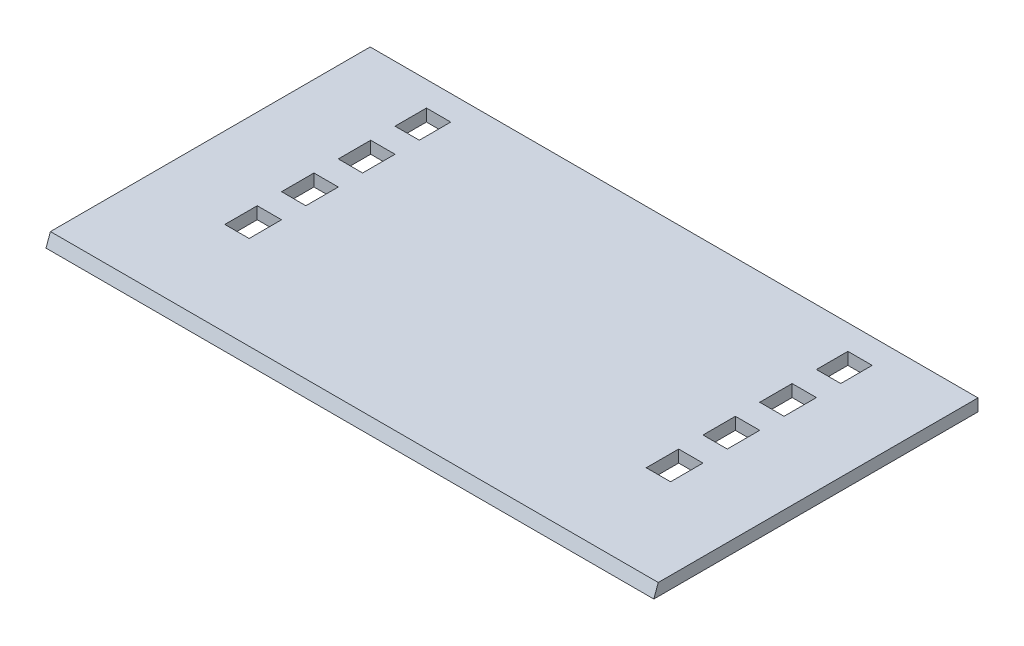
SolidWorks part; units mm, degrees
ref_plane "Plan de face" through (0, 0, 0) normal (0, 0, 1) x (1, 0, 0)
ref_plane "Plan de dessus" through (0, 0, 0) normal (0, 1, 0) x (1, 0, 0)
ref_plane "Plan de droite" through (0, 0, 0) normal (1, 0, 0) x (0, 0, -1)
sketch "Esquisse1" plane through (0, 0, 0) normal (0, 1, 0) x (1, 0, 0)
  line L1 (0, 0) -> (150, 0)
  line L2 (0, 0) -> (0, 80)
  line L3 (0, 80) -> (150, 80)
  line L4 (150, 0) -> (150, 80)
  dimension "D1" = 150
  dimension "D2" = 80
extrude "Boss.-Extru.1" add sketch "Esquisse1" along normal blind 3
chamfer "Chanfrein2" distance 3 angle 20 1 edges at (75, 3, 0) first distance on face at (75, 1.5, 0)
sketch "Esquisse2" plane through (0, 3, 0) normal (0, 1, 0) x (1, 0, 0)
  line L0 (20, 66.1284) -> (26, 66.1284) construction
  line L1 (124, 73.8859) -> (130, 73.8859)
  line L2 (124, 73.8859) -> (124, 66.1284)
  line L3 (124, 66.1284) -> (130, 66.1284)
  line L4 (130, 73.8859) -> (130, 66.1284)
  line L5 (130, 60.1284) -> (124, 60.1284)
  line L6 (130, 60.1284) -> (130, 52.1284)
  line L7 (130, 52.1284) -> (124, 52.1284)
  line L8 (124, 60.1284) -> (124, 52.1284)
  line L9 (130, 46.1284) -> (124, 46.1284)
  line L10 (130, 46.1284) -> (130, 38.1284)
  line L11 (130, 38.1284) -> (124, 38.1284)
  line L12 (124, 46.1284) -> (124, 38.1284)
  line L13 (124, 32.1284) -> (130, 32.1284)
  line L14 (124, 32.1284) -> (124, 24.1284)
  line L15 (124, 24.1284) -> (130, 24.1284)
  line L16 (130, 32.1284) -> (130, 24.1284)
  line L17 (20, 24.1284) -> (26, 24.1284)
  line L18 (20, 24.1284) -> (20, 32.1284)
  line L19 (20, 32.1284) -> (26, 32.1284)
  line L20 (26, 24.1284) -> (26, 32.1284)
  line L21 (26, 38.1284) -> (20, 38.1284)
  line L22 (26, 38.1284) -> (26, 46.1284)
  line L23 (26, 46.1284) -> (20, 46.1284)
  line L24 (20, 38.1284) -> (20, 46.1284)
  line L25 (20, 52.1284) -> (26, 52.1284)
  line L26 (20, 52.1284) -> (20, 60.1284)
  line L27 (20, 60.1284) -> (26, 60.1284)
  line L28 (26, 52.1284) -> (26, 60.1284)
  line L29 (20, 73.8859) -> (26, 73.8859)
  line L30 (20, 73.8859) -> (20, 66.1284)
  line L31 (20, 66.1284) -> (26, 66.1284)
  line L32 (26, 73.8859) -> (26, 66.1284)
  line L33 (26, 73.8859) -> (26, 66.1284) construction
extrude "Enlèv. mat.-Extru.1" cut sketch "Esquisse2" against normal blind 3
